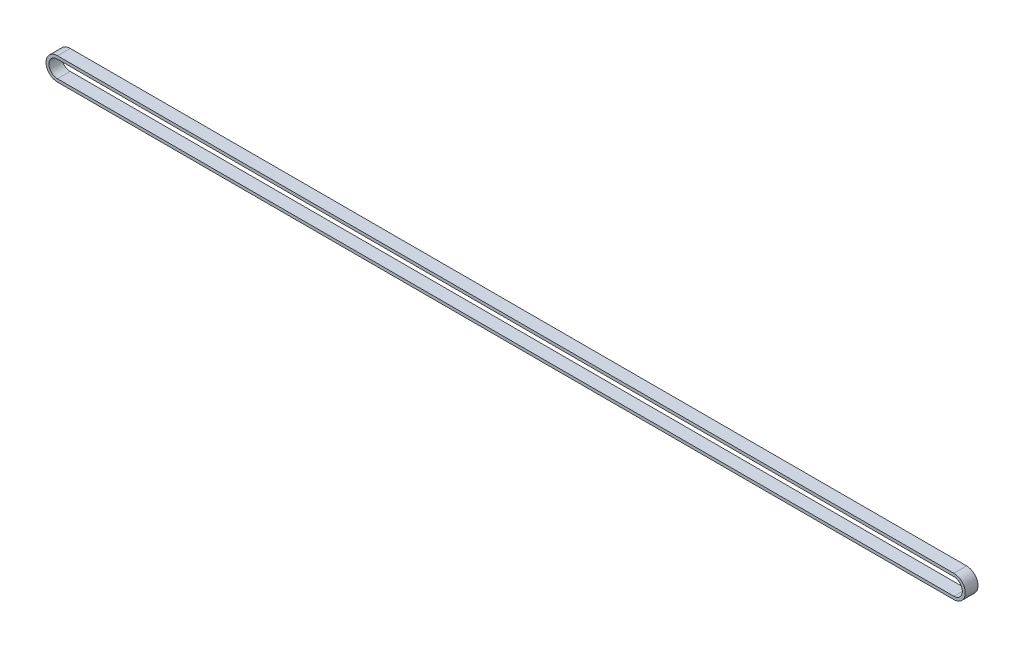
SolidWorks part; units mm, degrees
ref_plane "Front Plane" through (0, 0, 0) normal (0, 0, 1) x (1, 0, 0)
ref_plane "Top Plane" through (0, 0, 0) normal (0, 1, 0) x (1, 0, 0)
ref_plane "Right Plane" through (0, 0, 0) normal (1, 0, 0) x (0, 0, -1)
sketch "Sketch1" plane through (0, 0, 0) normal (0, 0, 1) x (1, 0, 0)
  line L0 (-211, 5.38) -> (211, 5.38)
  line L1 (-211, -4) -> (211, -4)
  line L3 (-211, 4) -> (211, 4)
  line L5 (-211, -4) -> (211, 4) construction
  line L6 (-211, 4) -> (211, -4) construction
  line L7 (-211, -5.38) -> (211, -5.38)
  arc A0 (-211, 4) -> (-211, -4) centre (-211, 0) ccw
  arc A1 (211, -4) -> (211, 4) centre (211, 0) ccw
  arc A2 (211, -5.38) -> (211, 5.38) centre (211, 0) ccw
  arc A3 (-211, 5.38) -> (-211, -5.38) centre (-211, 0) ccw
  point P0 (0, 0)
  dimension "D1" = 4
  dimension "D2" = 422
  dimension "D3" = 1.38
extrude "Boss-Extrude1" add sketch "Sketch1" along normal blind 6
